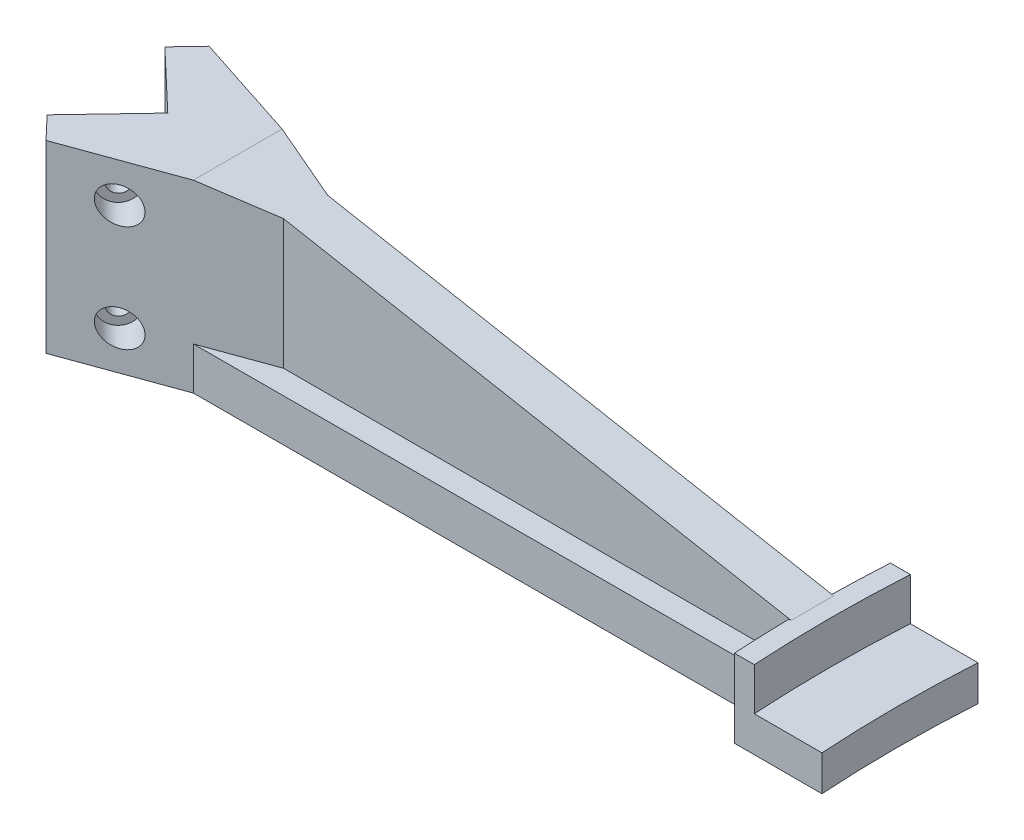
SolidWorks part; units mm, degrees
ref_plane "Front Plane" through (0, 0, 0) normal (0, 0, 1) x (1, 0, 0)
ref_plane "Top Plane" through (0, 0, 0) normal (0, 1, 0) x (1, 0, 0)
ref_plane "Right Plane" through (0, 0, 0) normal (1, 0, 0) x (0, 0, -1)
sketch "Sketch2" plane through (0, 0, 0) normal (0, 1, 0) x (1, 0, 0)
  line L0 (0, 0) -> (-181.1246, 0) construction
  line L1 (0, 0) -> (135.9511, 0) construction
  line L2 (-181.1246, 0) -> (-197.6966, 15.7434)
  line L3 (-197.6966, 15.7434) -> (-191.6108, 22.1496)
  line L4 (-191.6108, 22.1496) -> (-181.1246, 12.1877)
  line L5 (-181.1246, 12.1877) -> (-181.1246, 0)
  line L14 (0.6536, 22) -> (25.3402, 22)
  line L15 (0.6536, -22) -> (25.3402, -22)
  line L16 (25.3402, 22) -> (25.3402, -22) construction
  line L34 (-181.1246, 0) -> (-197.6966, -17.4443)
  line L49 (-197.6966, -17.4443) -> (-191.6108, -23.8504)
  line L50 (-191.6108, -23.8504) -> (-181.1246, -12.8123)
  line L51 (-181.1246, -12.8123) -> (-181.1246, 0)
  line L52 (-181.1246, 12.1877) -> (0.2109, 12.5)
  line L53 (-181.1246, -12.8123) -> (0.2109, -12.5)
  line L54 (0.2109, -12.5) -> (0.2109, 12.5) construction
  line L55 (-181.1246, 12.1877) -> (-181.1246, 24.2548) construction
  line L56 (-181.1246, -12.8123) -> (-181.1246, -19.1381)
  line L58 (-191.6108, 22.1496) -> (-161.1246, 12.2221)
  line L62 (-191.6108, -23.8504) -> (-161.1246, -12.7779)
  line L63 (-161.1246, 12.2221) -> (-161.1246, -12.7779)
  line L64 (-161.1246, -12.7779) -> (-124.8315, 0.4038)
  line L65 (-161.1246, 12.2221) -> (-124.8315, 0.4038)
  arc A0 (0.6536, 22) -> (0.6536, -22) centre (370.6, 0) ccw
  arc A1 (6.2636, 22) -> (6.2636, -22) centre (370.6, 0) ccw
  arc A2 (25.3402, 22) -> (25.3402, -22) centre (370.6, 0) ccw
  point P32 (5.6, 0)
  dimension "D2" = 365
  dimension "D3" = 5.6
  dimension "D4" = 19.04
  dimension "D7" = 25
  dimension "D5" = 133.531
  dimension "D6" = 136.469
  dimension "D8" = 25
  dimension "D9" = 44
  dimension "D10" = 20
  dimension "D18" = 46
  dimension "D19" = 186.7246
extrude "Boss-Extrude2" add sketch "Sketch2" against normal blind 12 contours A0 L52 L53 | L53 L52 | L53 | L52 | A1 L14 A0 L15 | L50 L51 L34 L49 | L5 L4 L3 L2 | L65 L63 L64 region at (-188.0032, 0, -12.1717) region at (-188.0032, 0, 13.1665) region at (-171.1246, 0, 0.2951) region at (-177.9533, 0, -15.5198) region at (-177.9533, 0, 16.4802) region at (-149.0269, 0, 0.0507) region at (-71.8375, 0, 0.1503) region at (3.0196, 0, 0)
extrude "Boss-Extrude3" add sketch "Sketch2<5>" along normal blind 10 from surface contours A2 L14 A1 L15 region at (15.3473, 0, 0) starting at face at (-97.5736, -12, 0.3044)
sketch "Sketch2<5>" plane through (0, 0, 0) normal (0, 1, 0) x (1, 0, 0) same geometry as "Sketch2"
extrude "Boss-Extrude4" add sketch "Sketch2<6>" along normal blind 22 from surface contours A1 L14 A0 L15 region at (3.0196, 0, 0) starting at face at (-94.6416, -12, 0.3044)
sketch "Sketch2<6>" plane through (0, 0, 0) normal (0, 1, 0) x (1, 0, 0) same geometry as "Sketch2"
extrude "Boss-Extrude7" add sketch "Sketch2<9>" along normal blind 40 contours L63 L52 L5 L51 L53 | L5 L4 L3 L2 | L58 L4 L52 | L50 L51 L34 L49 | L50 L62 L53 | L65 L63 L64 region at (-188.0032, 0, -12.1717) region at (-188.0032, 0, 13.1665) region at (-171.1246, 0, 0.2951) region at (-177.9533, 0, -15.5198) region at (-177.9533, 0, 16.4802) region at (-149.0269, 0, 0.0507)
sketch "Sketch2<9>" plane through (0, 0, 0) normal (0, 1, 0) x (1, 0, 0) same geometry as "Sketch2"
sketch "Sketch4" plane through (0, 0, 0) normal (0, 0, 1) x (1, 0, 0)
  line L2 (-197.6966, -12) -> (-197.6966, 40) construction
  line L5 (0.6536, 10) -> (-161.1246, 40)
  line L6 (-191.6108, 40) -> (-124.8315, 40) construction
  line L8 (-181.1246, 0) -> (0.2109, 0) construction
  line L9 (-161.1246, 0) -> (0.6536, 0)
  line L10 (0.6536, 0) -> (0.6536, 10)
  line L11 (0.6536, -12) -> (0.6536, 10) construction
  line L12 (0.6536, 10) -> (0, 10) construction
  line L13 (-161.1246, 40) -> (-161.1246, 0)
  dimension "D1" = 36.572
extrude "Boss-Extrude17" add sketch "Sketch4" along normal blind 6 and the other way blind 6
sketch "Sketch5" plane through (0, 0, 0) normal (0, 0, 1) x (1, 0, 0)
  line L0 (0.6536, 10) -> (-161.1246, 40) construction
  line L1 (0.6536, 10) -> (-161.1246, 40)
extrude "Cut-Extrude-Thin1" cut sketch "Sketch5" against normal through all and the other way through all thin contours L1 thin type one direction wall 10
sketch "Sketch6" plane through (-95.2035, 0, -90.4433) normal (-0.725, 0, -0.6887) x (-0.6887, 0, 0.725)
  line L0 (134.7494, 29) -> (134.7494, -1) construction
  line L1 (124.7494, 40) -> (148.8105, 40) construction
  line L2 (124.7494, 40) -> (144.7494, 40)
  line L3 (124.7494, 40) -> (124.7494, -12)
  line L4 (124.7494, -12) -> (144.7494, -12)
  line L5 (144.7494, 40) -> (144.7494, -12)
  line L6 (124.7494, 40) -> (144.7494, -12) construction
  line L7 (124.7494, -12) -> (144.7494, 40) construction
  line L8 (124.7494, -12) -> (124.7494, 40) construction
  line L9 (124.7494, -12) -> (148.8105, -12) construction
  circle A0 centre (134.7494, 29) radius 5
  circle A1 centre (134.7494, -1) radius 5
  circle A2 centre (134.7494, 29) radius 2.75
  circle A3 centre (134.7494, -1) radius 2.75
  point P3 (134.7494, 14)
  point P6 (134.7494, 14)
  dimension "D2" = 10
  dimension "D3" = 5.5
  dimension "D1" = 20
  dimension "D4" = 30
extrude "Cut-Extrude1" cut sketch "Sketch6" against normal through all from offset 8 contours A0 | A1 offset against normal yes
extrude "Cut-Extrude2" cut sketch "Sketch6<4>" against normal through all both and the other way through all contours A2 | A3
sketch "Sketch6<4>" plane through (-95.2035, 0, -90.4433) normal (-0.725, 0, -0.6887) x (-0.6887, 0, 0.725) same geometry as "Sketch6"
mirror "Mirror1" about plane through (0, 0, 0) normal (0, 0, 1) of "Cut-Extrude1", "Cut-Extrude2"
